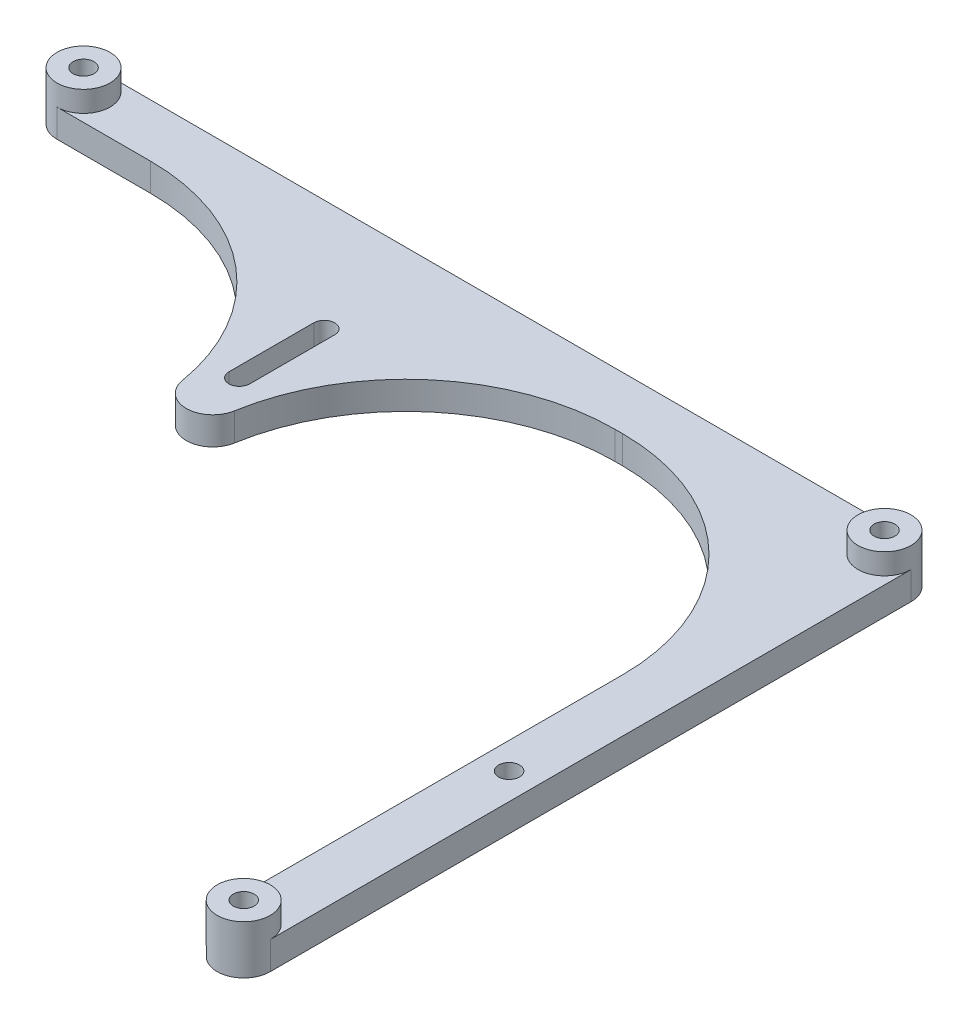
SolidWorks part; units mm, degrees
ref_plane "Front Plane" through (0, 0, 0) normal (0, 0, 1) x (1, 0, 0)
ref_plane "Top Plane" through (0, 0, 0) normal (0, 1, 0) x (1, 0, 0)
ref_plane "Right Plane" through (0, 0, 0) normal (1, 0, 0) x (0, 0, -1)
sketch "Sketch1" plane through (0, 0, 0) normal (0, 1, 0) x (1, 0, 0)
  line L0 (0, -46) -> (0, 46) construction
  line L1 (0, 46) -> (-115, 46) construction
  line L2 (-68.25, 46) -> (-68.25, 21.62) construction
  line L3 (-68.25, 33.81) -> (-68.25, 21.62) construction
  line L4 (-3.81, -49.81) -> (3.81, -49.81)
  line L5 (-3.81, -49.81) -> (-3.81, 49.81)
  line L6 (-3.81, 49.81) -> (3.81, 49.81)
  line L7 (3.81, -49.81) -> (3.81, 49.81)
  line L8 (-3.81, -49.81) -> (3.81, 49.81) construction
  line L9 (-3.81, 49.81) -> (3.81, -49.81) construction
  line L10 (3.81, 42.19) -> (-118.81, 42.19)
  line L11 (3.81, 42.19) -> (3.81, 49.81)
  line L12 (3.81, 49.81) -> (-118.81, 49.81)
  line L13 (-118.81, 42.19) -> (-118.81, 49.81)
  line L14 (3.81, 42.19) -> (-118.81, 49.81) construction
  line L15 (3.81, 49.81) -> (-118.81, 42.19) construction
  line L16 (-64.44, 49.81) -> (-72.06, 49.81)
  line L17 (-64.44, 49.81) -> (-64.44, 17.81)
  line L18 (-64.44, 17.81) -> (-72.06, 17.81)
  line L19 (-72.06, 49.81) -> (-72.06, 17.81)
  line L20 (-64.44, 49.81) -> (-72.06, 17.81) construction
  line L21 (-64.44, 17.81) -> (-72.06, 49.81) construction
  line L22 (-66.75, 33.81) -> (-66.75, 21.62)
  line L23 (-69.75, 33.81) -> (-69.75, 21.62)
  circle A0 centre (0, -46) radius 1.5
  circle A1 centre (0, -7.9) radius 1.5
  circle A2 centre (0, 46) radius 1.5
  circle A3 centre (-115, 46) radius 1.5
  circle A4 centre (-68.25, 26.1) radius 1.5
  circle A5 centre (-115, 46) radius 3.81
  circle A6 centre (-68.25, 26.1) radius 3.81
  circle A7 centre (0, -46) radius 3.81
  circle A8 centre (0, 46) radius 3.81
  arc A9 (-66.75, 33.81) -> (-69.75, 33.81) centre (-68.25, 33.81) ccw
  arc A10 (-69.75, 21.62) -> (-66.75, 21.62) centre (-68.25, 21.62) ccw
  circle A11 centre (-68.25, 17.81) radius 3.81
  point P6 (0, 0)
  point P11 (-57.5, 46)
  point P16 (-68.25, 33.81)
  point P33 (-68.25, 27.715)
  dimension "D1" = 3
  dimension "D2" = 38.1
  dimension "D3" = 92
  dimension "D4" = 115
  dimension "D9" = 34
  dimension "D5" = 68.25
  dimension "D6" = 7.62
  dimension "D7" = 7.62
  dimension "D8" = 7.62
  dimension "D10" = 32
extrude "Boss-Extrude1" add sketch "Sketch1" along normal blind 4 contours A7 L7 L10 L5 A1 | A7 A0 | A8 A2 | L12 L17 L10 L5 | A8 L6 L5 | A8 L5 L10 | A8 L10 L7 | A5 L10 L19 L12 | L12 L19 L10 L17 | A6 L17 L10 L19 | A5 A3 | L23 A6 | L22 A6 | A11 A10 L23 A6 L19 | A11 L17 A6 L22 A10 | L18 A11 | L18 A11 A10 region at (-2.6179, 0, 48.6179) region at (0, 0, 0.3306) region at (-34.125, 0, -46) region at (-2.959, 0, -43.041) region at (2.959, 0, -43.041) region at (-2.959, 0, -48.959) region at (-2.6179, 0, -48.6179) region at (-68.25, 0, -36.2045) region at (-68.25, 0, -46) region at (-92.0429, 0, -46) region at (-65.7968, 0, -26.1) region at (-65.2805, 0, -21.9548) region at (-117.6179, 0, -43.3821) region at (-71.2195, 0, -21.9548) region at (-70.7032, 0, -26.1) region at (-68.25, 0, -16.193) region at (-68.25, 0, -19.1777)
extrude "Boss-Extrude2" add sketch "Sketch1<3>" along normal blind 7 contours A5 A3 | A8 A2 | A7 A0 region at (-2.6179, 0, 48.6179) region at (-2.6179, 0, -48.6179) region at (-117.6179, 0, -43.3821)
sketch "Sketch1<3>" plane through (0, 0, 0) normal (0, 1, 0) x (1, 0, 0) same geometry as "Sketch1"
fillet "Fillet1" radius 30 3 edges at (-64.44, 2, -42.19) (-72.06, 2, -42.19) (-3.81, 2, -42.19)
